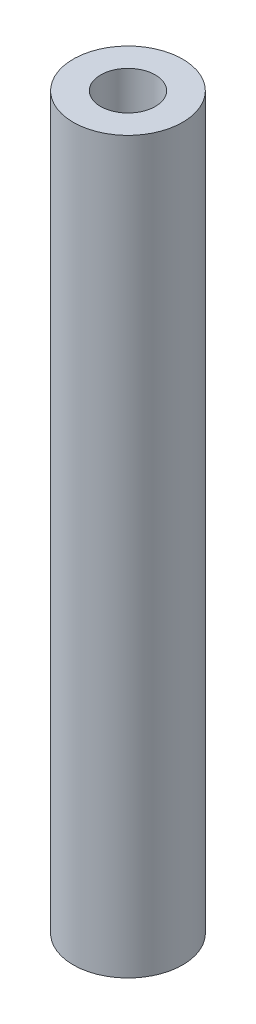
SolidWorks part; units mm, degrees
ref_plane "Front Plane" through (0, 0, 0) normal (0, 0, 1) x (1, 0, 0)
ref_plane "Top Plane" through (0, 0, 0) normal (0, 1, 0) x (1, 0, 0)
ref_plane "Right Plane" through (0, 0, 0) normal (1, 0, 0) x (0, 0, -1)
sketch "Sketch2" plane through (0, 0, 0) normal (0, 1, 0) x (1, 0, 0)
  circle A0 centre (-15.0841, 6.4658) radius 1.5
  circle A1 centre (-15.0841, 6.4658) radius 3
  dimension "D1" = 3
  dimension "D2" = 6
extrude "Boss-Extrude1" add sketch "Sketch2" along normal blind 40
